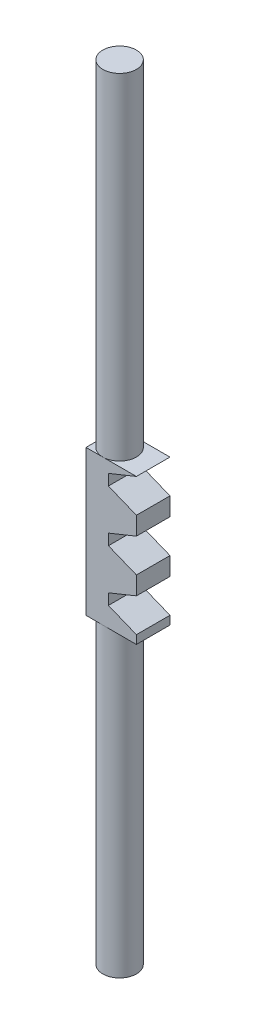
SolidWorks part; units mm, degrees
ref_plane "Front Plane" through (0, 0, 0) normal (0, 0, 1) x (1, 0, 0)
ref_plane "Top Plane" through (0, 0, 0) normal (0, 1, 0) x (1, 0, 0)
ref_plane "Right Plane" through (0, 0, 0) normal (1, 0, 0) x (0, 0, -1)
sketch "Sketch1" plane through (0, 0, 0) normal (0, 1, 0) x (1, 0, 0)
  circle A0 centre (0, 0) radius 1.5
  dimension "D1" = 3
extrude "Boss-Extrude1" add sketch "Sketch1" along normal blind 40
sketch "Sketch6" plane through (0, 0, 0) normal (0, 0, 1) x (1, 0, 0)
  line L5 (-1.5, 40) -> (3, 40)
  line L9 (3, 40) -> (3, 27)
  line L10 (-1.5, 40) -> (3, 40)
  line L11 (-1.5, 40) -> (-1.5, 27)
  line L12 (-1.5, 27) -> (3, 27)
  line L13 (3, 40) -> (3, 27)
  dimension "D2" = 13
extrude "Boss-Extrude2" add sketch "Sketch6" along normal blind 1.5 and the other way blind 1.5 contours L9 region at (0.75, 33.5, 0)
sketch "Sketch12" plane through (0, 0, 1.5) normal (0, 0, 1) x (1, 0, 0)
  line L0 (3, 40) -> (3, 37)
  line L1 (3, 40) -> (3, 27) construction
  line L2 (3, 37) -> (0.5, 38.0101)
  line L3 (3, 40) -> (0.5, 38.9899)
  line L4 (0.5, 38.9899) -> (0.5, 38.0101)
  line L5 (0.5, 34.3699) -> (0.5, 33.3901)
  line L6 (3, 35.38) -> (3, 32.38)
  line L7 (3, 32.38) -> (0.5, 33.3901)
  line L8 (3, 35.38) -> (0.5, 34.3699)
  line L9 (0.5, 29.7499) -> (0.5, 28.7701)
  line L10 (3, 30.76) -> (3, 27.76)
  line L11 (3, 27.76) -> (0.5, 28.7701)
  line L12 (3, 30.76) -> (0.5, 29.7499)
  dimension "D1" = 292
  dimension "D2" = 292
  dimension "D3" = 2.5
  dimension "D4" = 2.5
  dimension "D5" = 3
  dimension "D6" = 3
extrude "Cut-Extrude2" cut sketch "Sketch12" against normal blind 4
sketch "Sketch13" plane through (0, 40, 0) normal (0, 1, 0) x (1, 0, 0)
  circle A0 centre (0, 0) radius 1.5
  dimension "D1" = 3
extrude "Boss-Extrude3" add sketch "Sketch13" along normal blind 30
